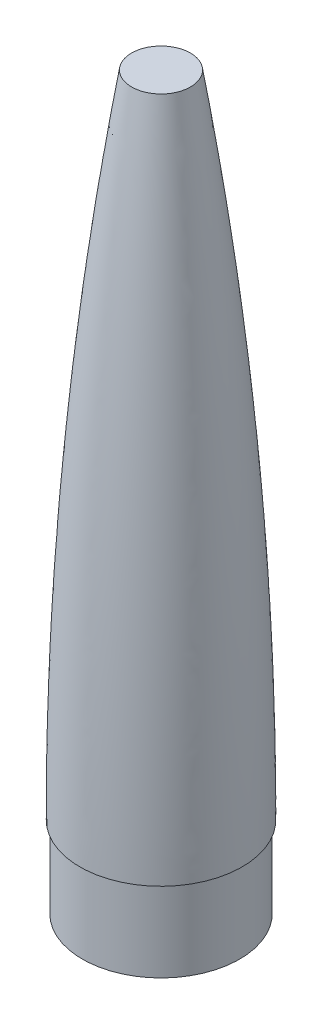
SolidWorks part; units mm, degrees
material "E-Glass Fiber"
ref_plane "Front Plane" through (0, 0, 0) normal (0, 0, 1) x (1, 0, 0)
ref_plane "Top Plane" through (0, 0, 0) normal (0, 1, 0) x (1, 0, 0)
ref_plane "Right Plane" through (0, 0, 0) normal (1, 0, 0) x (0, 0, -1)
sketch "Sketch1" plane through (0, 0, 0) normal (0, 0, 1) x (1, 0, 0)
  line L1 (0, 0) -> (0, 812.8)
  line L2 (-101.6, 0) -> (0, 0) construction
  line L3 (0, 812.8) -> (-36.8107, 812.8)
  line L4 (0, 1016) -> (0, 812.8) construction
  line L5 (-98.425, 0) -> (-98.425, -101.6)
  line L6 (-98.425, -101.6) -> (0, -101.6)
  line L7 (0, 0) -> (0, -101.6)
  line L8 (-98.425, 0) -> (-101.6, 0)
  arc A0 (0, 1016) -> (-36.8107, 812.8) centre (5029.2, 0) ccw construction
  spline S0 degree 4 poles (-23.2398, 893.2866) (-23.5393, 891.5924) (-24.137, 888.2033) (-25.0296, 883.1148) (-26.2088, 876.3394) (-27.3767, 869.5744) (-28.525, 862.8715) (-29.6693, 856.1347) (-30.7805, 849.5464) (-31.9198, 842.7267) (-32.9792, 836.3481) (-34.1672, 829.1125) (-35.0792, 823.5406) (-36.435, 815.1441) (-37.0457, 811.3406) (-38.406, 802.8129) (-39.4063, 796.4669) (-40.5094, 789.4175) (-41.5637, 782.6088) (-42.4113, 777.0973) (-43.2542, 771.5761) (-44.0966, 766.0177) (-44.9373, 760.4296) (-45.7763, 754.8098) (-46.8172, 747.7841) (-48.054, 739.3514) (-49.4786, 729.5106) (-51.8836, 712.6352) (-56.1784, 681.6809) (-64.3109, 619.7097) (-79.957, 484.2341) (-91.5619, 342.6137) (-98.2797, 206.3794) (-100.6652, 101.2886) (-101.1219, 71.4617) (-101.3057, 55.1272) (-101.3623, 49.4455) (-101.4013, 45.2149) (-101.437, 41.0149) (-101.474, 36.1352) (-101.5101, 30.575) (-101.5403, 25.0243) (-101.5644, 19.4326) (-101.5824, 13.9273) (-101.5945, 8.4855) (-101.6008, 1.478) (-101.6004, -2.3538) (-101.5919, -10.831) (-101.5742, -16.4582) (-101.5477, -23.7538) (-101.5124, -30.1968) (-101.4682, -37.0784) (-101.4152, -43.7331) (-101.3531, -50.5363) (-101.2817, -57.3091) (-101.201, -64.1452) (-101.1107, -70.9945) (-101.0361, -76.1392) (-100.9833, -79.5663) (-100.9562, -81.2797) knots 0 0 0 0 0 0.007031 0.014061 0.021092 0.028122 0.035027 0.041932 0.048837 0.055742 0.062647 0.069552 0.076457 0.083362 0.08904 0.094718 0.106073 0.111751 0.117429 0.123106 0.128784 0.134587 0.14039 0.146193 0.151996 0.163602 0.175208 0.186814 0.221632 0.291267 0.430538 0.743898 0.801928 0.848352 0.859958 0.865761 0.868662 0.871564 0.877241 0.882919 0.888597 0.894275 0.899952 0.90563 0.911308 0.916985 0.923861 0.930737 0.937613 0.944488 0.951364 0.95824 0.965115 0.971991 0.978993 0.985996 0.992998 1 1 1 1 1 construction
  spline S1 degree 4 poles (-36.8107, 812.8) (-36.9943, 811.656) (-37.3629, 809.3523) (-38.406, 802.8129) (-39.4063, 796.4669) (-40.5094, 789.4175) (-41.5637, 782.6088) (-42.4113, 777.0973) (-43.2542, 771.5761) (-44.0966, 766.0177) (-44.9373, 760.4296) (-45.7763, 754.8098) (-46.8172, 747.7841) (-48.054, 739.3514) (-49.4786, 729.5106) (-51.8836, 712.6352) (-56.1784, 681.6809) (-64.3109, 619.7097) (-79.957, 484.2341) (-91.5619, 342.6137) (-98.2797, 206.3794) (-100.6652, 101.2886) (-101.1219, 71.4617) (-101.3057, 55.1272) (-101.3623, 49.4455) (-101.4013, 45.2149) (-101.437, 41.0149) (-101.474, 36.1352) (-101.5101, 30.575) (-101.5403, 25.0243) (-101.5644, 19.4326) (-101.5824, 13.9273) (-101.5945, 8.4855) (-101.599, 3.4932) (-101.6, 1.1586) (-101.6, 0) knots 0.083362 0.083362 0.083362 0.083362 0.083362 0.08904 0.094718 0.106073 0.111751 0.117429 0.123106 0.128784 0.134587 0.14039 0.146193 0.151996 0.163602 0.175208 0.186814 0.221632 0.291267 0.430538 0.743898 0.801928 0.848352 0.859958 0.865761 0.868662 0.871564 0.877241 0.882919 0.888597 0.894275 0.899952 0.90563 0.911308 0.916985 0.916985 0.916985 0.916985 0.916985
  dimension "D2" = 1016
  dimension "D1" = 203.2
  dimension "D3" = 101.6
  dimension "D4" = 3.175
revolve "Revolve1" add sketch "Sketch1" angle 360 about L1 region at (-43.2688, 298.0469, 0)
shell "Shell1" thickness 3.175 removed face at (0, -101.6, -98.425)
equation "\"R\"= 4in"
equation "\"L\"= 40in"
equation "\"D2@Sketch1\" = \"L\""
equation "\"p\"= ( \"R\" ^ 2 + \"L\" ^ 2 ) / ( \"R\" * 2 )"
equation "\"tip_Length\"= ( \"R\" * 2 )"
equation "\"D1@Sketch1\"=\"tip_Length\""
